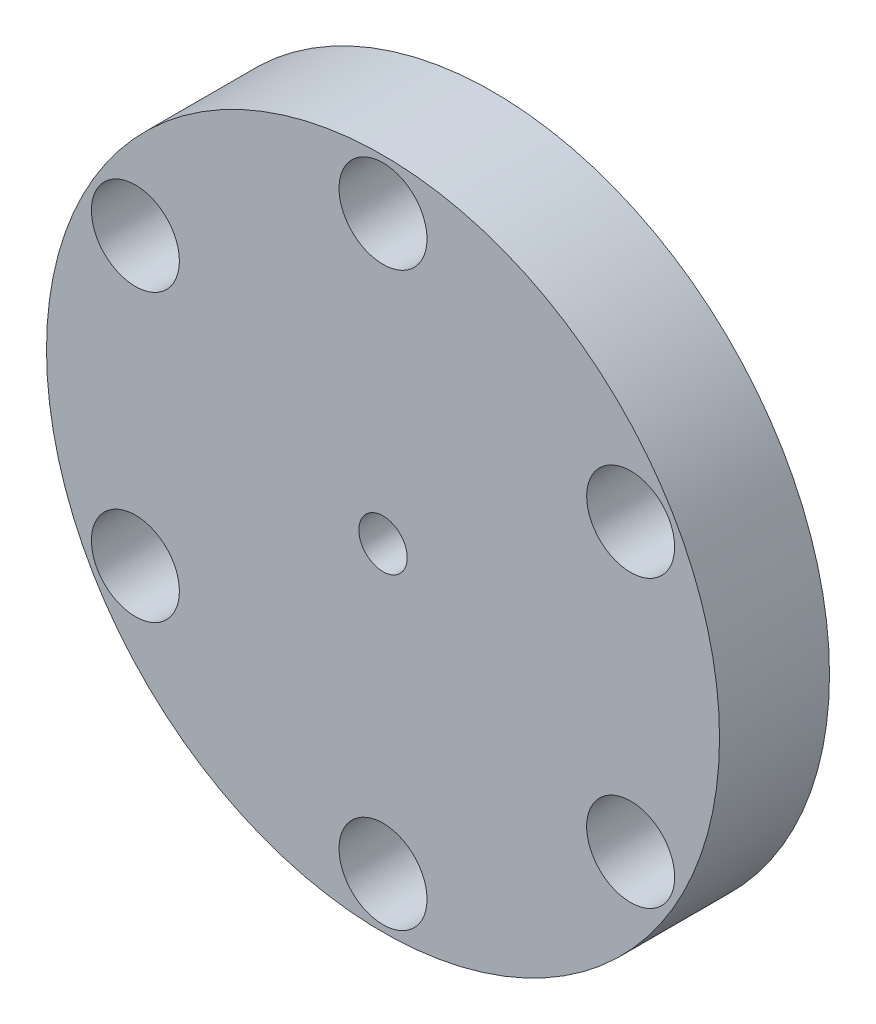
SolidWorks part; units mm, degrees
ref_plane "前视基准面" through (0, 0, 0) normal (0, 0, 1) x (1, 0, 0)
ref_plane "上视基准面" through (0, 0, 0) normal (0, 1, 0) x (1, 0, 0)
ref_plane "右视基准面" through (0, 0, 0) normal (1, 0, 0) x (0, 0, -1)
other "Configuration Table"
sketch "草图1" plane through (0, 0, 0) normal (0, 0, 1) x (1, 0, 0)
  circle A2 centre (0, 0) radius 18.85
  circle A3 centre (0, 0) radius 15.3
  circle A4 centre (0, 0) radius 1.1
  dimension "D1" = 37.7
  dimension "D2" = 30.6
  dimension "D3" = 2.2
extrude "凸台-拉伸1" add sketch "草图1" along normal mid plane 5 contours A3 | A4
sketch "草图2" plane through (0, 0, 2.5) normal (0, 0, 1) x (1, 0, 0)
  circle A0 centre (0, 13) radius 1.25
  circle A1 centre (0, 13) radius 2
  dimension "D1" = 2.5
  dimension "D3" = 4
  dimension "D2" = 13
extrude "切除-拉伸1" cut sketch "草图2" against normal through all contours A0
extrude "切除-拉伸2" cut sketch "草图2<2>" against normal offset from surface (3 mm away) 2 contours A1 up to face at (1.25, 13, -2.5)
sketch "草图2<2>" plane through (0, 0, 2.5) normal (0, 0, 1) x (1, 0, 0) same geometry as "草图2"
pattern_circular "阵列(圆周)1" count 6 over 360 about axis through (0, 0, 2.5) along (0, 0, -1) of "切除-拉伸1", "切除-拉伸2"
